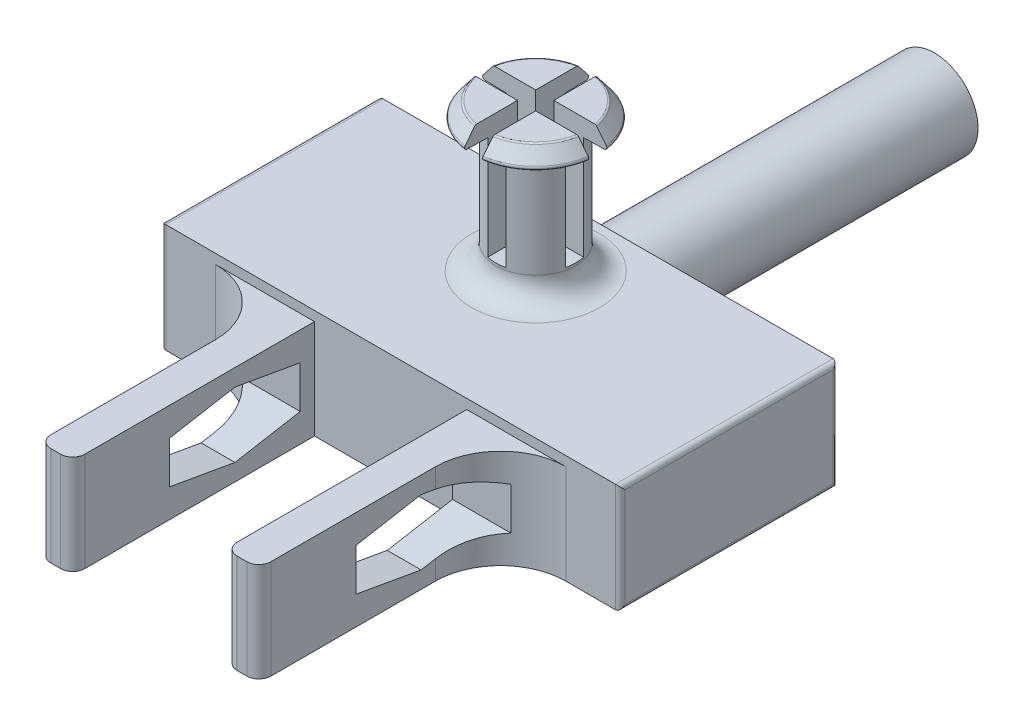
SolidWorks part; units mm, degrees
ref_plane "Front Plane" through (0, 0, 0) normal (0, 0, 1) x (1, 0, 0)
ref_plane "Top Plane" through (0, 0, 0) normal (0, 1, 0) x (1, 0, 0)
ref_plane "Right Plane" through (0, 0, 0) normal (1, 0, 0) x (0, 0, -1)
sketch "Szkic1" plane through (0, 0, 0) normal (0, 1, 0) x (1, 0, 0)
  line L0 (0, -13.1707) -> (0, 4.5) construction
  line L1 (4.55, -4.5) -> (-4.55, -4.5)
  line L2 (9.5, -4.5) -> (9.5, 4.5)
  line L3 (9.5, 4.5) -> (-9.5, 4.5)
  line L4 (-9.5, -4.5) -> (-9.5, 4.5)
  line L5 (9.5, -4.5) -> (-9.5, 4.5) construction
  line L6 (9.5, 4.5) -> (-9.5, -4.5) construction
  line L7 (-9.5, -4.5) -> (-4.55, -4.5)
  line L10 (2.5793, 4.5) -> (-2.5793, 4.5)
  line L13 (-4.55, -4.5) -> (-7.25, -4.5)
  line L14 (-4.55, -4.5) -> (-3.15, -4.5)
  line L15 (-4.55, -4.5) -> (-4.55, -14.5)
  line L16 (-4.55, -14.5) -> (-3.15, -14.5)
  line L17 (-3.15, -4.5) -> (-3.15, -14.5)
  line L18 (4.55, -4.5) -> (3.15, -4.5)
  line L19 (4.55, -4.5) -> (4.55, -14.5)
  line L20 (4.55, -14.5) -> (3.15, -14.5)
  line L21 (3.15, -4.5) -> (3.15, -14.5)
  line L22 (4.55, -4.5) -> (9.5, -4.5)
  line L23 (-4.55, -4.5) -> (-4.55, -7.2)
  line L26 (4.55, -4.5) -> (7.25, -4.5)
  line L27 (4.55, -4.5) -> (4.55, -7.2)
  arc A0 (-4.55, -7.2) -> (-7.25, -4.5) centre (-7.25, -7.2) ccw
  arc A1 (7.25, -4.5) -> (4.55, -7.2) centre (7.25, -7.2) ccw
  point P0 (0, 0)
  dimension "D1" = 9
  dimension "D2" = 19
  dimension "D3" = 10
  dimension "D4" = 1.4
  dimension "D5" = 6.3
  dimension "D6" = 2.7
extrude "Dodanie-wyciągnięcie1" add sketch "Szkic1" along normal blind 4.5 contours L1 L22 L2 L3 L4 L7 region at (0, 0, 0)
extrude "Dodanie-wyciągnięcie2" add sketch "Szkic1<7>" along normal blind 4.1 contours A0 L15 L7 | L17 L1 L15 L16 | A1 L22 L19 | L1 L21 L20 L19 region at (3.85, 0, 9.5) region at (5.1531, 0, 5.1031) region at (-3.85, 0, 9.5) region at (-5.1531, 0, 5.1031)
sketch "Szkic1<7>" plane through (0, 0, 0) normal (0, 1, 0) x (1, 0, 0) same geometry as "Szkic1"
ref_plane "Płaszczyzna1" through (0, 0, -4.5) normal (0, 0, -1) x (-1, 0, 0)
sketch "Szkic2" plane through (0, 0, -4.5) normal (0, 0, -1) x (-1, 0, 0)
  line L0 (0, 0) -> (0, 4.5) construction
  line L1 (-9.5, 4.5) -> (9.5, 4.5) construction
  circle A0 centre (0, 2.25) radius 1.8
  point P5 (0, 2.25)
  dimension "D1" = 3.6
extrude "Dodanie-wyciągnięcie3" add sketch "Szkic2" along normal blind 13.5
ref_plane "Płaszczyzna2" through (-3.15, 0, 0) normal (1, 0, 0) x (0, 0, -1)
sketch "Szkic3" plane through (-3.15, 0, 0) normal (1, 0, 0) x (0, 0, -1)
  line L0 (-7.79, 3.4) -> (-10.49, 2.9239)
  line L1 (-10.49, 2.9239) -> (-10.49, 1.1761)
  line L2 (-10.49, 1.1761) -> (-7.79, 0.7)
  line L3 (-7.79, 0.7) -> (-5.09, 1.1761)
  line L4 (-5.09, 1.1761) -> (-5.09, 2.9239)
  line L5 (-5.09, 2.9239) -> (-7.79, 3.4)
  line L7 (-4.5, 4.1) -> (-14.5, 4.1) construction
  line L8 (-4.5, 0) -> (-14.5, 0) construction
  dimension "D1" = 0.7
  dimension "D2" = 0.7
  dimension "D3" = 100
  dimension "D4" = 100
  dimension "D5" = 5.4
extrude "Wytnij-wyciągnięcie2" cut sketch "Szkic3" along normal through all both and the other way through all
fillet "Zaokrąglenie1" radius 0.5 4 edges at (3.15, 2.05, 14.5) (4.55, 2.05, 14.5) (-4.55, 2.05, 14.5) (-3.15, 2.05, 14.5)
fillet "Zaokrąglenie2" radius 0.2 8 edges at (-9.5, 2.25, -4.5) (-9.5, 4.5, 0) (9.5, 0, 0) (-9.5, 2.25, 4.5) (9.5, 2.25, 4.5) (9.5, 2.25, -4.5) (9.5, 4.5, 0) (-9.5, 0, 0)
ref_plane "Płaszczyzna3" through (0, 4.5, 0) normal (0, 1, 0) x (1, 0, 0)
sketch "Szkic4" plane through (0, 4.5, 0) normal (0, 1, 0) x (1, 0, 0)
  line L0 (-9.3, 1.5) -> (9.3, 1.5) construction
  line L1 (2.475, 4.5) -> (-2.475, 4.5) construction
  line L3 (-9.3, 4.5) -> (-9.3, -4.5) construction
  line L4 (9.3, -4.5) -> (9.3, 4.5) construction
  circle A0 centre (0, 1.5) radius 1.65
  point P6 (0, 1.5)
  dimension "D1" = 3.3
  dimension "D2" = 3
extrude "Dodanie-wyciągnięcie4" add sketch "Szkic4" along normal blind 5.1
ref_plane "Płaszczyzna4" through (0, 9.6, 0) normal (0, 1, 0) x (1, 0, 0)
sketch "Szkic5" plane through (0, 9.6, 0) normal (0, 1, 0) x (1, 0, 0)
  line L0 (0, 3.15) -> (0, -0.15) construction
  circle A0 centre (0, 1.5) radius 1.65 construction
  circle A1 centre (0, 1.5) radius 1.65
  point P5 (0, 1.5)
  dimension "D1" = 3.3
extrude "Dodanie-wyciągnięcie5" add sketch "Szkic5" along normal blind 1
fillet "Zaokrąglenie4" radius 1 1 edges at (0, 4.5, 0.15)
ref_axis "Oś1" through (0, 16.6, -1.5) along (0, -1, 0)
ref_point "Punkt1"
ref_point "Punkt2"
ref_plane "Płaszczyzna5" through (0, 0, 0) normal (1, 0, 0) x (0, 0, -1)
ref_plane "Płaszczyzna Dolnia" through (0, 0, 0) normal (0, -1, 0) x (-1, 0, 0)
ref_plane "Płaszczyzna6" through (0, 10.5, 0) normal (0, 1, 0) x (1, 0, 0)
ref_plane "Płaszczyzna7" through (0, 10.6, 0) normal (0, 1, 0) x (1, 0, 0)
sketch "Szkic6" plane through (0, 10.6, 0) normal (0, 1, 0) x (1, 0, 0)
  line L0 (0.375, 4.6645) -> (0.375, 1.875)
  line L1 (-0.375, 4.6645) -> (-0.375, 1.875)
  line L2 (3.1645, 1.875) -> (0.375, 1.875)
  line L3 (3.1645, 1.125) -> (0.375, 1.125)
  line L4 (-0.375, 1.125) -> (-3.1645, 1.125)
  line L5 (-0.375, 1.875) -> (-3.1645, 1.875)
  line L6 (0.375, 1.125) -> (0.375, -1.6645)
  line L7 (-0.375, 1.125) -> (-0.375, -1.6645)
  line L8 (-0.375, 1.875) -> (0.375, 1.125) construction
  arc A4 (0.375, 4.6645) -> (-0.375, 4.6645) centre (0, 1.5) ccw
  arc A5 (3.1645, 1.125) -> (3.1645, 1.875) centre (0, 1.5) ccw
  arc A6 (-0.375, -1.6645) -> (0.375, -1.6645) centre (0, 1.5) ccw
  arc A7 (-3.1645, 1.875) -> (-3.1645, 1.125) centre (0, 1.5) ccw
  point P18 (0, 1.5)
  dimension "D1" = 0.75
  dimension "D2" = 0.75
sketch "Szkic7" plane through (0, 0, 0) normal (1, 0, 0) x (0, 0, -1)
  line L0 (3.15, 10.6) -> (3.65, 10.6)
  line L1 (4.6866, 10.6) -> (4.6645, 10.6) construction
  line L2 (3.15, 5.5) -> (3.15, 10.6) construction
  line L3 (3.65, 10.6) -> (4.1978, 9.9)
  line L4 (4.1978, 9.9) -> (3.15, 9.8817)
  line L6 (3.15, 5.5) -> (3.15, 10.6) construction
  line L7 (3.15, 9.8817) -> (3.15, 10.6)
  line L9 (3.15, 5.5) -> (3.15, 10.6) construction
  line L10 (3.15, 5.5) -> (3.15, 10.6) construction
  line L11 (3.15, 5.5) -> (3.15, 10.6) construction
  line L13 (4.95, 4.5) -> (-4.95, 4.5) construction
  dimension "D1" = 5.4
  dimension "D2" = 89
  dimension "D3" = 0.5
revolve "Obrót1" add sketch "Szkic7" angle 360 about axis through (0, 16.6, -1.5) along (0, -1, 0)
fillet "Zaokrąglenie5" radius 0.1 2 edges at (0, 10.6, 0.65) (0, 9.9, 1.1978)
extrude "Wytnij-wyciągnięcie3" cut sketch "Szkic6" against normal blind 5
